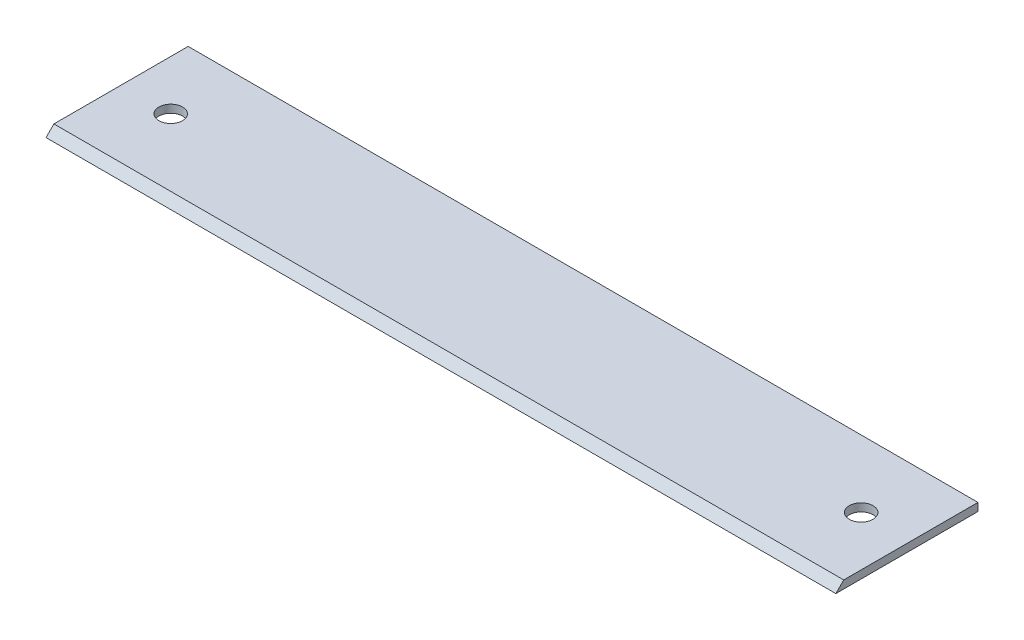
SolidWorks part; units mm, degrees
ref_plane "Спереди" through (0, 0, 0) normal (0, 0, 1) x (1, 0, 0)
ref_plane "Сверху" through (0, 0, 0) normal (0, 1, 0) x (1, 0, 0)
ref_plane "Справа" through (0, 0, 0) normal (1, 0, 0) x (0, 0, -1)
sketch "Эскиз1" plane through (0, 0, 0) normal (0, 1, 0) x (1, 0, 0)
  line L1 (-50, -9) -> (50, -9)
  line L2 (-50, -9) -> (-50, 9)
  line L3 (-50, 9) -> (50, 9)
  line L4 (50, -9) -> (50, 9)
  line L5 (-50, -9) -> (50, 9) construction
  line L6 (-50, 9) -> (50, -9) construction
  point P0 (0, 0)
  dimension "D1" = 100
  dimension "D2" = 18
extrude "Бобышка-Вытянуть1" add sketch "Эскиз1" along normal blind 1
chamfer "Фаска1" distance 1 angle 45 1 edges at (0, 1, 9)
sketch "Эскиз2" plane through (0, 1, 0) normal (0, 1, 0) x (1, 0, 0)
  line L0 (-50, 0.5) -> (50, 0.5) construction
  line L1 (-50, 9) -> (-50, -8) construction
  line L2 (50, -8) -> (50, 9) construction
  line L4 (-31, 2.5) -> (-21, 2.5)
  line L5 (-31, 2.5) -> (-31, -1.5)
  line L6 (-31, -1.5) -> (-21, -1.5)
  line L7 (-21, 2.5) -> (-21, -1.5)
  line L8 (-31, 2.5) -> (-21, -1.5) construction
  line L9 (-31, -1.5) -> (-21, 2.5) construction
  line L10 (21, 2.5) -> (31, 2.5)
  line L11 (21, 2.5) -> (21, -1.5)
  line L12 (21, -1.5) -> (31, -1.5)
  line L13 (31, 2.5) -> (31, -1.5)
  line L14 (21, 2.5) -> (31, -1.5) construction
  line L15 (21, -1.5) -> (31, 2.5) construction
  point P6 (-26, 0.5)
  point P11 (26, 0.5)
  dimension "D1" = 21
  dimension "D2" = 42
  dimension "D3" = 4
  dimension "D4" = 4
  dimension "D5" = 10
  dimension "D6" = 10
sketch "Эскиз3" plane through (0, 1, 0) normal (0, 1, 0) x (1, 0, 0)
  line L0 (-50, 0.5) -> (50, 0.5) construction
  line L1 (-50, 9) -> (-50, -8) construction
  line L2 (50, -8) -> (50, 9) construction
  line L3 (0, 9) -> (0, -8) construction
  line L4 (50, 9) -> (-50, 9) construction
  line L5 (-50, -8) -> (50, -8) construction
  circle A0 centre (-43.7097, 0.5) radius 1.5
  circle A1 centre (43.7097, 0.5) radius 1.5
extrude "Вырез-Вытянуть2" cut sketch "Эскиз3" against normal blind 20
